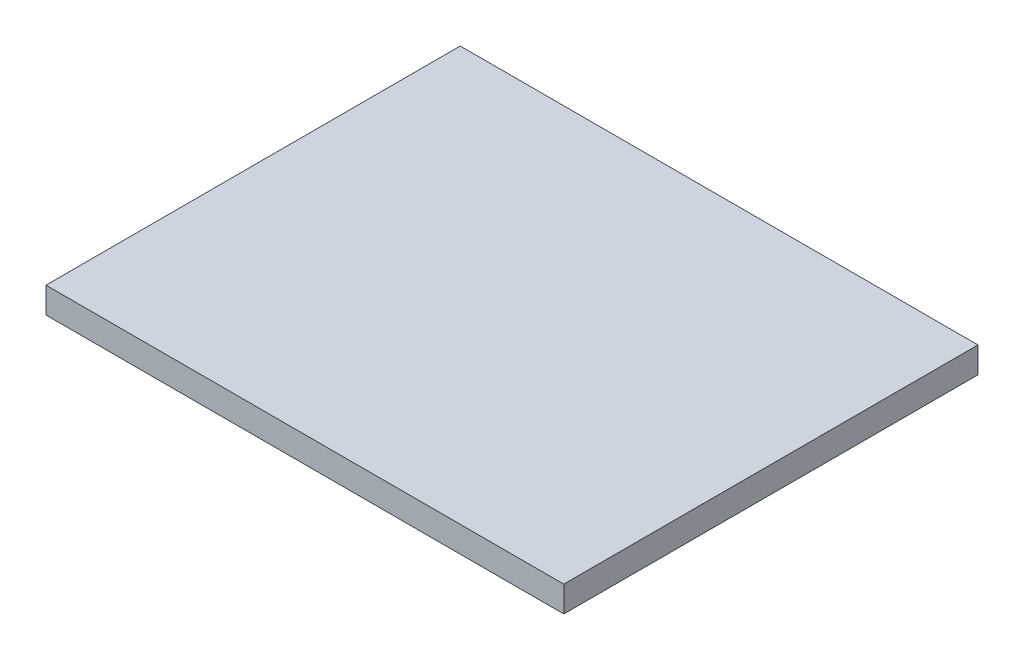
SolidWorks part; units mm, degrees
ref_plane "Ebene vorne" through (0, 0, 0) normal (0, 0, 1) x (1, 0, 0)
ref_plane "Ebene oben" through (0, 0, 0) normal (0, 1, 0) x (1, 0, 0)
ref_plane "Ebene rechts" through (0, 0, 0) normal (1, 0, 0) x (0, 0, -1)
sketch "Skizze1" plane through (0, 0, 0) normal (0, 0, 1) x (1, 0, 0)
  line L1 (0, 0) -> (1000, 0)
  line L2 (0, 0) -> (0, 50)
  line L3 (0, 50) -> (1000, 50)
  line L4 (1000, 0) -> (1000, 50)
  dimension "D1" = 50
  dimension "D2" = 1000
extrude "Aufsatz-Linear austragen1" add sketch "Skizze1" along normal blind 800
